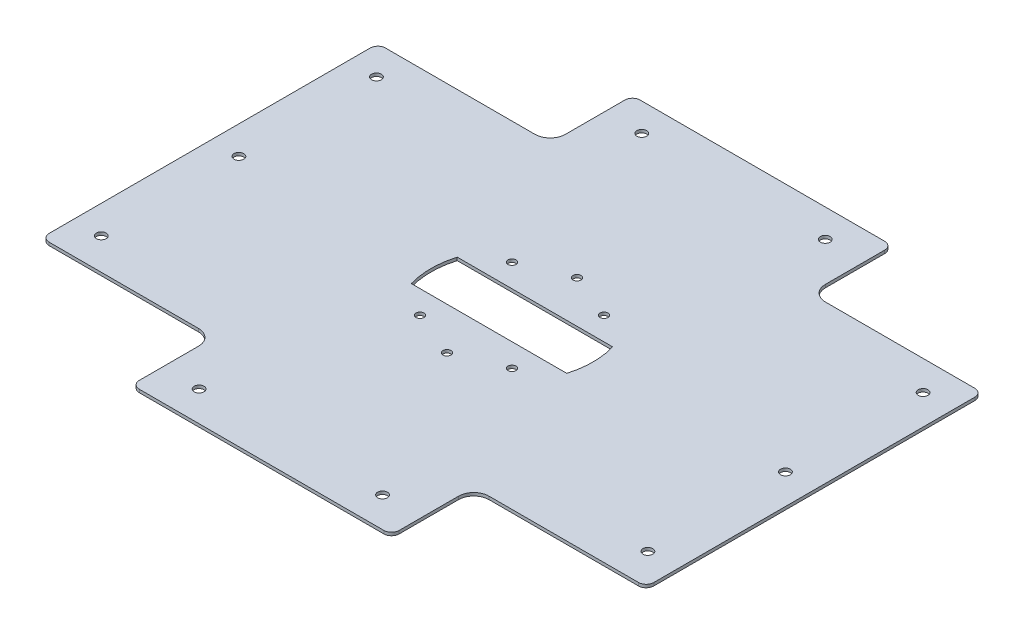
SolidWorks part; units mm, degrees
material "7075-T6, Пластина (SS)"
ref_plane "Спереди" through (0, 0, 0) normal (0, 0, 1) x (1, 0, 0)
ref_plane "Сверху" through (0, 0, 0) normal (0, 1, 0) x (1, 0, 0)
ref_plane "Справа" through (0, 0, 0) normal (1, 0, 0) x (0, 0, -1)
sketch "Эскиз1" plane through (0, 0, 0) normal (0, 1, 0) x (1, 0, 0)
  line L1 (-80, -163.8055) -> (80, -163.8055)
  line L2 (-197.7687, -105) -> (-197.7687, 105)
  line L3 (-80, 163.8055) -> (80, 163.8055)
  line L4 (197.7687, -105) -> (197.7687, 105)
  line L5 (-236.4266, 144.4996) -> (-147.9018, 144.4996) construction
  line L6 (-147.9018, 144.4996) -> (286.4952, 144.4996) construction
  line L18 (-284.5497, 0) -> (284.3305, 0) construction
  line L19 (-160.9018, 110) -> (-134.9018, 110)
  line L20 (-160.9018, 110) -> (-160.9018, 0)
  line L21 (-160.9018, 0) -> (-134.9018, 0)
  line L22 (-134.9018, 110) -> (-134.9018, 0)
  line L23 (-147.9018, -182.6295) -> (-147.9018, 219.9923) construction
  line L24 (-160.9018, 0) -> (-134.9018, 0)
  line L25 (-160.9018, 0) -> (-160.9018, -110)
  line L26 (-160.9018, -110) -> (-134.9018, -110)
  line L27 (-134.9018, 0) -> (-134.9018, -110)
  line L28 (-97.9018, -119.4996) -> (-197.9018, -119.4996)
  line L29 (-97.9018, 169.4996) -> (-197.9018, 169.4996)
  line L30 (-97.9018, 169.4996) -> (-97.9018, 119.4996)
  line L31 (-97.9018, 119.4996) -> (-197.9018, 119.4996)
  line L32 (-197.9018, 169.4996) -> (-197.9018, 119.4996)
  line L33 (-97.9018, 169.4996) -> (-197.9018, 119.4996) construction
  line L34 (-97.9018, 119.4996) -> (-197.9018, 169.4996) construction
  line L35 (-197.9018, -169.4996) -> (-197.9018, -119.4996)
  line L36 (-97.9018, -169.4996) -> (-197.9018, -169.4996)
  line L37 (-97.9018, -169.4996) -> (-97.9018, -119.4996)
  line L39 (-85, 120) -> (-85, 158.8055)
  line L40 (0, 262.7398) -> (0, -186.5795) construction
  line L41 (-192.7687, 110) -> (-95, 110)
  line L43 (-192.7687, -110) -> (-95, -110)
  line L44 (-85, -120) -> (-85, -158.8055)
  line L45 (85, 120) -> (85, 158.8055)
  line L46 (192.7687, 110) -> (95, 110)
  line L47 (192.7687, -110) -> (95, -110)
  line L48 (85, -120) -> (85, -158.8055)
  line L49 (97.9018, -169.4996) -> (97.9018, -119.4996)
  line L50 (97.9018, -169.4996) -> (197.9018, -169.4996)
  line L51 (197.9018, -169.4996) -> (197.9018, -119.4996)
  line L52 (97.9018, -119.4996) -> (197.9018, -119.4996)
  line L53 (160.9018, 0) -> (160.9018, -110)
  line L54 (160.9018, -110) -> (134.9018, -110)
  line L55 (134.9018, 0) -> (134.9018, -110)
  line L56 (160.9018, 0) -> (134.9018, 0)
  line L57 (160.9018, 110) -> (160.9018, 0)
  line L58 (160.9018, 0) -> (134.9018, 0)
  line L59 (134.9018, 110) -> (134.9018, 0)
  line L60 (160.9018, 110) -> (134.9018, 110)
  line L61 (97.9018, 119.4996) -> (197.9018, 119.4996)
  line L62 (197.9018, 169.4996) -> (197.9018, 119.4996)
  line L63 (97.9018, 169.4996) -> (197.9018, 169.4996)
  line L64 (97.9018, 169.4996) -> (97.9018, 119.4996)
  arc A0 (85, -120) -> (95, -110) centre (95, -120) cw
  arc A1 (85, 120) -> (95, 110) centre (95, 120) ccw
  arc A2 (-95, -110) -> (-85, -120) centre (-95, -120) cw
  arc A3 (-85, 120) -> (-95, 110) centre (-95, 120) cw
  arc A4 (192.7687, -110) -> (197.7687, -105) centre (192.7687, -105) ccw
  arc A5 (85, -158.8055) -> (80, -163.8055) centre (80, -158.8055) cw
  arc A6 (-85, -158.8055) -> (-80, -163.8055) centre (-80, -158.8055) ccw
  arc A7 (-192.7687, -110) -> (-197.7687, -105) centre (-192.7687, -105) cw
  arc A8 (-192.7687, 110) -> (-197.7687, 105) centre (-192.7687, 105) ccw
  arc A9 (197.7687, 105) -> (192.7687, 110) centre (192.7687, 105) ccw
  arc A10 (85, 158.8055) -> (80, 163.8055) centre (80, 158.8055) ccw
  arc A11 (-85, 158.8055) -> (-80, 163.8055) centre (-80, 158.8055) cw
  circle A12 centre (59.4553, 145.4623) radius 3.2
  circle A13 centre (59.4553, -144.1486) radius 3.2
  circle A14 centre (-60.5447, -144.1486) radius 3.2
  circle A15 centre (-60.5447, 145.4623) radius 3.2
  circle A16 centre (-179.3134, 90.6569) radius 3.2
  circle A17 centre (-179.3134, -89.3431) radius 3.2
  circle A18 centre (-179.3134, 0.6569) radius 3.2
  circle A19 centre (178.224, 90.6569) radius 3.2
  circle A20 centre (178.224, 0.6569) radius 3.2
  circle A21 centre (178.224, -89.3431) radius 3.2
  point P0 (0, 0)
  point P3 (85, -110)
  point P17 (-147.9018, 110)
  point P18 (-147.9018, 110)
  point P20 (-147.9018, 0)
  point P22 (-150, 134)
  point P37 (-147.9018, 144.4996)
  point P46 (85, 110)
  point P52 (-85, -110)
  point P55 (-85, 110)
  point P56 (-147.9018, 0)
  point P77 (197.7687, -110)
  point P80 (85, -163.8055)
  point P83 (-85, -163.8055)
  point P86 (-197.7687, -110)
  point P89 (-197.7687, 110)
  point P92 (197.7687, 110)
  point P95 (85, 163.8055)
  point P98 (-85, 163.8055)
  dimension "D2" = 50
  dimension "D6" = 10
  dimension "D4" = 5
  dimension "D3" = 26
  dimension "D5" = 338.9991
  dimension "D7" = 395.5373
  dimension "D8" = 110
  dimension "D9" = 170
  dimension "D10" = 100
  dimension "D13" = 9.4996
  dimension "D14" = 12.9018
sketch "Эскиз2" plane through (0, 0, 0) normal (0, 1, 0) x (1, 0, 0)
  line L0 (-162.9105, 114) -> (-136.9105, 114)
  line L1 (-162.9105, 114) -> (-162.9105, 0)
  line L2 (-162.9105, 0) -> (-136.9105, 0)
  line L3 (-136.9105, 114) -> (-136.9105, 0)
  line L4 (-149.9105, -192.6295) -> (-149.9105, 209.9923) construction
  line L5 (-162.9105, 0) -> (-136.9105, 0)
  line L6 (-162.9105, 0) -> (-162.9105, -114)
  line L7 (-162.9105, -114) -> (-136.9105, -114)
  line L8 (-136.9105, 0) -> (-136.9105, -114)
  line L9 (-99.9105, -123.5568) -> (-199.9105, -123.5568)
  line L10 (-99.9105, 163.4996) -> (-199.9105, 163.4996)
  line L11 (-99.9105, 163.4996) -> (-99.9105, 123.4996)
  line L12 (-99.9105, 123.4996) -> (-199.9105, 123.4996)
  line L13 (-199.9105, 163.4996) -> (-199.9105, 123.4996)
  line L14 (-199.9105, -163.5568) -> (-199.9105, -123.5568)
  line L15 (-99.9105, -163.5568) -> (-199.9105, -163.5568)
  line L16 (-99.9105, -163.5568) -> (-99.9105, -123.5568)
  line L17 (-284.5497, 0) -> (284.3305, 0) construction
  point P11 (-149.9105, 0)
  point P12 (-149.9105, 0)
sketch "Эскиз3" plane through (0, 0, 0) normal (0, 1, 0) x (1, 0, 0)
  line L0 (-89.8176, -177.9027) -> (70.2405, -177.9027)
  line L1 (-209.7886, -106.9112) -> (-209.7886, 106.8353)
  line L2 (-80.029, 172.0973) -> (50.2405, 172.0973)
  line L3 (170.2114, -106.9112) -> (170.2114, 103.9123)
  line L4 (-87.1938, 124.0033) -> (-87.1938, 164.9326)
  line L5 (-202.6239, 114) -> (-97.1971, 114)
  line L6 (-202.6239, -114.076) -> (-106.9857, -114.076)
  line L7 (-96.9823, -124.0793) -> (-96.9823, -170.738)
  line L8 (57.4052, 121.0803) -> (57.4052, 164.9326)
  line L9 (163.0467, 111.077) -> (67.4085, 111.077)
  line L10 (163.0467, -114.076) -> (87.4085, -114.076)
  line L11 (77.4052, -124.0793) -> (77.4052, -170.738)
  line L13 (-162.9105, 114) -> (-136.9105, 114) construction
  arc A0 (77.4052, -124.0793) -> (87.4085, -114.076) centre (87.4085, -124.0793) cw
  arc A1 (57.4052, 121.0803) -> (67.4085, 111.077) centre (67.4085, 121.0803) ccw
  arc A2 (-106.9857, -114.076) -> (-96.9823, -124.0793) centre (-106.9857, -124.0793) cw
  arc A3 (-87.1938, 124.0033) -> (-97.1971, 114) centre (-97.1971, 124.0033) cw
  arc A4 (-80.029, 172.0973) -> (-87.1938, 164.9326) centre (-80.029, 164.9326) ccw
  arc A5 (50.2405, 172.0973) -> (57.4052, 164.9326) centre (50.2405, 164.9326) cw
  arc A6 (170.2114, 103.9123) -> (163.0467, 111.077) centre (163.0467, 103.9123) ccw
  arc A7 (170.2114, -106.9112) -> (163.0467, -114.076) centre (163.0467, -106.9112) cw
  arc A8 (70.2405, -177.9027) -> (77.4052, -170.738) centre (70.2405, -170.738) ccw
  arc A9 (-89.8176, -177.9027) -> (-96.9823, -170.738) centre (-89.8176, -170.738) cw
  arc A10 (-209.7886, -106.9112) -> (-202.6239, -114.076) centre (-202.6239, -106.9112) ccw
  arc A11 (-209.7886, 106.8353) -> (-202.6239, 114) centre (-202.6239, 106.8353) cw
  point P36 (115.2276, 111.077)
  point P39 (-149.9105, 114)
  point P42 (-149.9105, 114)
  dimension "D3" = 10.0033
  dimension "D4" = 7.1647
  dimension "D1" = 380
  dimension "D2" = 350
  dimension "D5" = 112.8062
  dimension "D6" = 63.8267
  dimension "D7" = 61.0203
extrude "Бобышка-Вытянуть1" add sketch "Эскиз1" along normal blind 2 separate body contours A11 L39 A3 L41 L22 L27 L43 A2 L44 A6 L1 A5 L48 A0 L47 L55 L59 L46 A1 L45 A10 L3 | L4 A9 L46 L57 L53 L47 A4 | L46 L59 L56 L57 | L53 L56 L55 L47 | L27 L21 L25 L26 | L41 A8 L2 A7 L43 L25 L20 | L22 L19 L20 L21 region at (0.0009, 0, 0.0011) region at (-147.9018, 0, 55) region at (147.9018, 0, 55) region at (-176.8353, 0, 107.7693) region at (-147.9018, 0, -55) region at (163.1325, 0, 55) region at (147.9018, 0, -55)
sketch "Эскиз4" plane through (0, 2, 0) normal (0, 1, 0) x (1, 0, 0)
  line L0 (197.7687, 0) -> (-197.7687, 0) construction
  line L1 (197.7687, -105) -> (197.7687, 105) construction
  line L2 (-197.7687, -105) -> (-197.7687, 105) construction
  line L3 (197.7687, 0) -> (10, 0) construction
  line L4 (-22, 0) -> (0, 0) construction
  line L5 (0, 0) -> (0, 42.54) construction
  circle A1 centre (0, 42.54) radius 2.6
  circle A2 centre (0, -42.54) radius 2.6
  circle A7 centre (0, 0) radius 42.54 construction
  circle A8 centre (30.0803, 30.0803) radius 2.6
  circle A9 centre (-30.0803, -30.0803) radius 2.6
  circle A10 centre (-30.0803, 30.0803) radius 2.6
  circle A11 centre (30.0803, -30.0803) radius 2.6
  point P14 (0, 0)
  point P21 (0, 0)
  point P26 (0, 0)
  point P29 (0, 0)
  dimension "D1" = 2
  dimension "D2" = 5.2
  dimension "D3" = 2
  dimension "D4" = 2
extrude "Вырез-Вытянуть1" cut sketch "Эскиз4" against normal through all
sketch "Эскиз5" plane through (0, 0, 0) normal (0, -1, 0) x (1, 0, 0)
  line L0 (50.8331, -15) -> (-50.8331, -15)
  line L7 (50.8331, 15) -> (-50.8331, 15)
  arc A0 (50.8331, -15) -> (50.8331, 15) centre (0, 0) ccw
  arc A1 (-50.8331, 15) -> (-50.8331, -15) centre (0, 0) ccw
  point P0 (0, 0)
  dimension "D2" = 101.6661
  dimension "D3" = 101.6661
  dimension "D1" = 30
extrude "Вырез-Вытянуть2" cut sketch "Эскиз5" against normal through all
